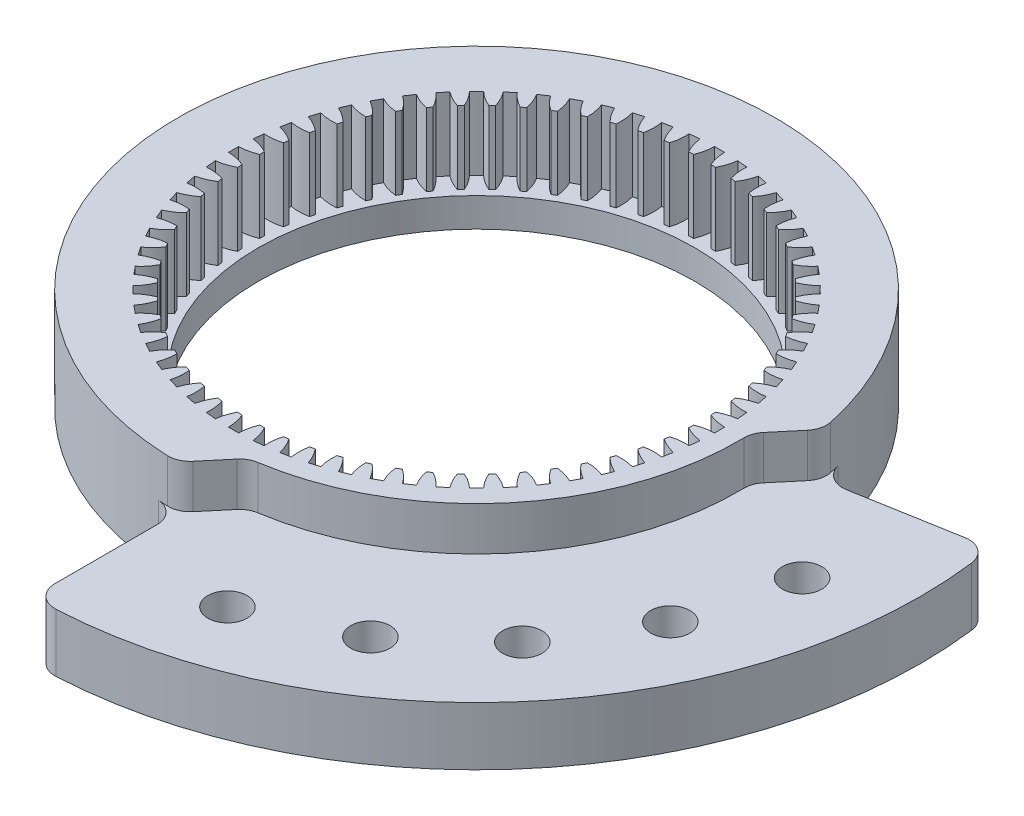
SolidWorks part; units mm, degrees
ref_plane "Front Plane" through (0, 0, 0) normal (0, 0, 1) x (1, 0, 0)
ref_plane "Top Plane" through (0, 0, 0) normal (0, 1, 0) x (1, 0, 0)
ref_plane "Right Plane" through (0, 0, 0) normal (1, 0, 0) x (0, 0, -1)
sketch "Sketch1" plane through (0, 0, 0) normal (0, 1, 0) x (1, 0, 0)
  circle A0 centre (0, 0) radius 16
  circle A1 centre (0, 0) radius 16.7
  circle A2 centre (0, 0) radius 15.5
  dimension "D1" = 32
  dimension "D2" = 33.4
  dimension "D3" = 1.2
extrude "Boss-Extrude1" add sketch "Sketch1" along normal mid plane 5 contours A1 A0 | A0 A2 | A2 region at (-15.5475, 0, 0) region at (-16.2277, 0, 0) region at (0, 0, 0)
sketch "Sketch7" plane through (0, 0, 0) normal (0, 1, 0) x (1, 0, 0)
  line L0 (16.7, 0) -> (-16.7, 0) construction
  line L1 (0, 16.7) -> (0, -16.7) construction
  circle A0 centre (0, 0) radius 16.7 construction
  point P7 (0, 0)
sketch "Sketch4" plane through (0, 0, 0) normal (0, 1, 0) x (1, 0, 0)
  line L0 (0, 0) -> (0, -30.5) construction
  line L10 (0, 0) -> (30.0366, 5.2963) construction
  line L11 (30.0366, 5.2963) -> (20.1886, 3.5598)
  line L12 (0, -30.5) -> (0, -20.5)
  circle A2 centre (0, 0) radius 15.5 construction
  circle A3 centre (0, 0) radius 15.5
  arc A4 (20.1886, 3.5598) -> (0, -20.5) centre (0, 0) ccw
  circle A9 centre (0, 0) radius 30.5 construction
  arc A10 (30.0366, 5.2963) -> (0, -30.5) centre (0, 0) cw
  dimension "D1" = 5
  dimension "D3" = 100
  dimension "D2" = 10
extrude "Boss-Extrude2" add sketch "Sketch4" along normal mid plane 5
sketch "Sketch3" plane through (0, 0, 0) normal (0, 1, 0) x (1, 0, 0)
  line L0 (0, 0) -> (0, 16.7) construction
  line L1 (-0.3927, 15.9952) -> (0.3927, 15.9952) construction
  line L2 (-0.3434, 15.4962) -> (0, 0) construction
  line L3 (0, 13.7683) -> (-0.5155, 16.692) construction
  line L4 (0, 0) -> (0.8194, 16.6799) construction
  line L5 (0.3927, 15.9952) -> (1.177, 15.9566) construction
  line L6 (0, 15.5) -> (0, 16.7) construction
  line L7 (0.3434, 15.4962) -> (0.3434, 16.7) construction
  line L8 (0.3434, 16.0981) -> (-0.3121, 16.0981) construction
  arc A1 (-0.5957, 16.6894) -> (-0.3434, 15.4962) centre (-3.6364, 15.4232) cw construction
  arc A2 (0.5957, 16.6894) -> (0.3434, 15.4962) centre (3.6364, 15.4232) ccw construction
  circle A3 centre (0, 0) radius 15.5 construction
  arc A4 (0.3434, 15.4962) -> (-0.3434, 15.4962) centre (0, 0) ccw construction
  circle A5 centre (0, 0) radius 16 construction
  circle A6 centre (0, 0) radius 16.7 construction
  arc A7 (0.5957, 15.5068) -> (-0.5957, 15.5068) centre (0, 32.1962) cw
  arc A8 (0.5957, 16.6894) -> (-0.5957, 16.6894) centre (0, 0) ccw construction
  arc A9 (-0.5957, 15.5068) -> (-0.3434, 16.7) centre (-3.6364, 16.773) ccw
  arc A10 (0.5957, 15.5068) -> (0.3434, 16.7) centre (3.6364, 16.773) cw
  arc A11 (0.3434, 16.7) -> (-0.3434, 16.7) centre (0, 32.1962) cw
  dimension "D3" = 2.813
  dimension "D2" = 10
extrude "Cut-Extrude1" cut sketch "Sketch3" against normal through all both and the other way through all
pattern_circular "CirPattern1" count 64 over 360 about axis through (0, 2.5, 0) along (0, 1, 0) of "Cut-Extrude1"
sketch "Sketch5" plane through (0, 0, 0) normal (0, 1, 0) x (1, 0, 0)
  circle A0 centre (0, 0) radius 15.5183
extrude "Cut-Extrude2" cut sketch "Sketch5" against normal through all both and the other way through all
sketch "Sketch8" plane through (0, -2.5, 0) normal (0, -1, 0) x (1, 0, 0)
  line L2 (0, 30.5) -> (0, 20.5)
  line L6 (0, 30.5) -> (0, 20.5)
  line L8 (20.1886, -3.5598) -> (30.0366, -5.2963)
  line L9 (20.1886, -3.5598) -> (30.0366, -5.2963)
  circle A0 centre (0, 0) radius 15
  arc A3 (30.0366, -5.2963) -> (0, 30.5) centre (0, 0) ccw
  arc A4 (30.0366, -5.2963) -> (0, 30.5) centre (0, 0) ccw
  arc A5 (0, 20.5) -> (20.1886, -3.5598) centre (0, 0) ccw
  arc A7 (0, 20.5) -> (20.1886, -3.5598) centre (0, 0) ccw
  dimension "D2" = 30
  dimension "D1" = 0
extrude "Boss-Extrude3" add sketch "Sketch8" along normal blind 2
sketch "Sketch6" plane through (0, 2.5, 0) normal (0, 1, 0) x (1, 0, 0)
  line L0 (0, 0) -> (7.3135, -24.4287) construction
  line L2 (0, -16.7) -> (0, 16.7) construction
  line L4 (0, -20.5) -> (0, -30.5) construction
  circle A3 centre (7.3135, -24.4287) radius 0.5
  point P5 (0, -25.5)
  point P11 (0, 0)
  dimension "D2" = 16.667
  dimension "D1" = 1
  dimension "D3" = 25.5
extrude "Cut-Extrude3" cut sketch "Sketch6" against normal through all
pattern_circular "CirPattern2" count 5 over 66.667 about axis through (0, -2.5, 0) along (0, -1, 0) of "Cut-Extrude3" reverse direction yes
sketch "Sketch9" plane through (0, 2.5, 0) normal (0, 1, 0) x (1, 0, 0)
  line L0 (20.1886, 3.5598) -> (17.9763, 0.9233)
  line L1 (0, -20.5) -> (2.2123, -17.8635)
  line L2 (0, 0) -> (16.4873, -13.8345) construction
  line L3 (2.2123, -17.8635) -> (17.9763, 0.9233) construction
  line L4 (20.1886, 3.5598) -> (30.0366, 5.2963)
  line L5 (0, -20.5) -> (0, -30.5)
  line L6 (0, 0) -> (135.2451, 0) construction
  line L7 (30.0366, 5.2963) -> (20.1886, 3.5598) construction
  arc A0 (2.2123, -17.8635) -> (17.9763, 0.9233) centre (0, 0) ccw
  arc A1 (0, -30.5) -> (30.0366, 5.2963) centre (0, 0) ccw construction
  arc A2 (0, -30.5) -> (30.0366, 5.2963) centre (0, 0) ccw
  point P5 (10.0943, -8.4701)
  dimension "D1" = 36
extrude "Cut-Extrude4" cut sketch "Sketch9" against normal offset from surface (3 mm away) 4 up to face at (14.1559, -4.5, 21.7839)
fillet "Fillet1" radius 1.5 6 edges at (20.1886, -2.5, -3.5598) (30.0366, -2.5, -5.2963) (0, -2.5, 30.5) (0, -2.5, 20.5) (17.9763, 1, -0.9233) (2.2123, 1, 17.8635)
fillet "Fillet2" radius 1.5 2 edges at (0, 1, 20.5) (20.1886, 1, -3.5598)
hole_wizard "CSK for M2.5 Countersunk Flat Head Screw1" positions "Sketch12" profile "Sketch11" countersink size "M2.5" standard "ISO"
sketch "Sketch12" plane through (0, -4.5, 0) normal (0, -1, 0) x (-1, 0, 0)
  point P0 (-7.3135, -24.4287)
  point P3 (-14.0125, -21.3049)
  point P6 (-19.5341, -16.3911)
  point P9 (-23.4145, -10.1)
  point P16 (-25.3276, -2.9604)
sketch "Sketch11" plane through (7.3135, -4.5, 24.4287) normal (1, 0, 0) x (0, 0, -1)
  line L0 (0, 0) -> (0, 4.8112)
  line L1 (0, 4.8112) -> (1.35, 4)
  line L2 (1.35, 4) -> (1.35, 1.4)
  line L3 (1.35, 1.4) -> (2.75, 0)
  line L5 (2.75, 0) -> (0, 0)
  line L6 (-1.35, 1.4) -> (-2.75, 0) construction
  line L10 (0, 4.8112) -> (-1.35, 4) construction
  line L11 (0, -6.35) -> (0, 107.95) construction
  dimension "Hole Dia." = 2.7
  dimension "Hole Depth" = 4
  dimension "Near C'Sink Dia." = 5.5
  dimension "Near C'Sink Angle" = 90
  dimension "Drill Angle" = 118
ref_axis "Axis2" through (0, -4.5, 0) along (0, 1, 0)
equation "\"Module\"= .5"
equation "\"Number of Teeth\"=64"
equation "\"D1@Sketch1\"=\"Module\"* \"Number of Teeth\""
equation "\"D2@Sketch1\"=(\"Number of Teeth\" + 2) * \"Module\" + .4"
equation "\"D3@Sketch1\"=\"Module\" * if( \"Module\" => 1.25, 2.25, 2.4)"
equation "\"D3@Sketch3\"=180 / \"Number of Teeth\""
equation "\"D1@CirPattern1\"=\"Number of Teeth\""
